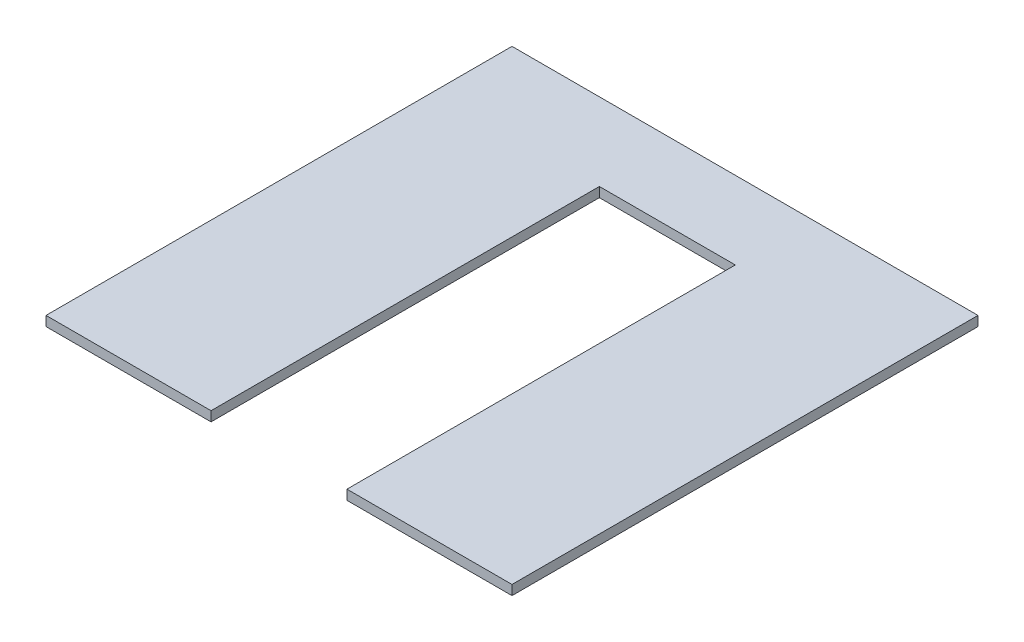
SolidWorks part; units mm, degrees
ref_plane "Front Plane" through (0, 0, 0) normal (0, 0, 1) x (1, 0, 0)
ref_plane "Top Plane" through (0, 0, 0) normal (0, 1, 0) x (1, 0, 0)
ref_plane "Right Plane" through (0, 0, 0) normal (1, 0, 0) x (0, 0, -1)
sketch "Sketch1" plane through (0, 0, 0) normal (0, 1, 0) x (1, 0, 0)
  line L0 (0, -55) -> (0, 55) construction
  line L1 (-152.4, -25.4) -> (152.4, -25.4)
  line L2 (-152.4, -25.4) -> (-152.4, 25.4)
  line L3 (-152.4, 25.4) -> (152.4, 25.4)
  line L4 (152.4, -25.4) -> (152.4, 25.4)
  line L5 (-152.4, -25.4) -> (152.4, 25.4) construction
  line L6 (-152.4, 25.4) -> (152.4, -25.4) construction
  line L7 (-152.4, -25.4) -> (-31.75, -25.4)
  line L8 (-152.4, -25.4) -> (-152.4, -279.4)
  line L9 (-152.4, -279.4) -> (-31.75, -279.4)
  line L10 (-31.75, -25.4) -> (-31.75, -279.4)
  line L11 (31.75, -25.4) -> (31.75, -279.4)
  line L12 (152.4, -279.4) -> (31.75, -279.4)
  line L13 (152.4, -25.4) -> (152.4, -279.4)
  line L14 (152.4, -25.4) -> (31.75, -25.4)
  line L15 (-44.45, -25.4) -> (-44.45, -279.4)
  line L16 (44.45, -25.4) -> (44.45, -279.4)
  point P0 (0, 0)
  dimension "D1" = 304.8
  dimension "D2" = 50.8
  dimension "D3" = 304.8
  dimension "D4" = 120.65
  dimension "D5" = 12.7
extrude "Boss-Extrude1" add sketch "Sketch1" along normal blind 6.35 contours L15 L1 L8 L9 | L14 L16 L12 L13 | L1 L7 L14 L4 L3 L2 region at (0, 0, 0) region at (-98.425, 0, 152.4) region at (98.425, 0, 152.4)
